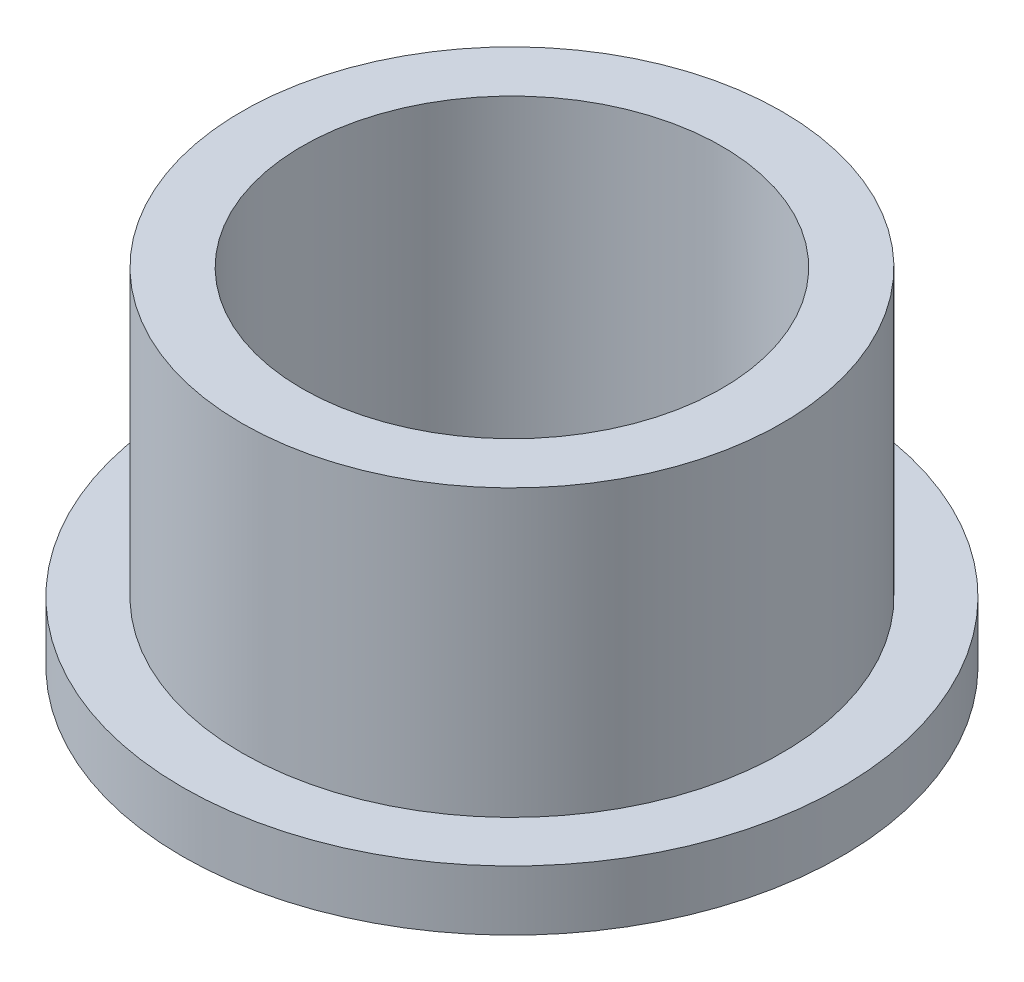
SolidWorks part; units mm, degrees
ref_plane "Front" through (0, 0, 0) normal (0, 0, 1) x (1, 0, 0)
ref_plane "Top" through (0, 0, 0) normal (0, 1, 0) x (1, 0, 0)
ref_plane "Right" through (0, 0, 0) normal (1, 0, 0) x (0, 0, -1)
sketch "Sketch1" plane through (0, 0, 0) normal (0, 1, 0) x (1, 0, 0)
  circle A0 centre (0, 0) radius 7.005
  circle A1 centre (0, 0) radius 9.015
  circle A2 centre (0, 0) radius 11
  dimension "ID" = 14.01
  dimension "OD" = 18.03
  dimension "FlangeOD" = 22
sketch "Sketch2" plane through (0, 0, 0) normal (0, 1, 0) x (1, 0, 0)
  circle A0 centre (0, 0) radius 7.005 construction
  circle A1 centre (0, 0) radius 9.015 construction
  circle A2 centre (0, 0) radius 7.005
  circle A3 centre (0, 0) radius 9.015
extrude "Boss-Extrude1" add sketch "Sketch2" along normal blind 14
sketch "Sketch3" plane through (0, 0, 0) normal (0, 1, 0) x (1, 0, 0)
  circle A0 centre (0, 0) radius 11 construction
  circle A1 centre (0, 0) radius 9.015 construction
  circle A2 centre (0, 0) radius 11
  circle A3 centre (0, 0) radius 9.015
extrude "Boss-Extrude2" add sketch "Sketch3" along normal blind 2
ref_axis "Center Axis 1" through (0, 14, 0) along (0, -1, 0)
sketch "Sketch4" plane through (0, 14, 0) normal (0, 1, 0) x (1, 0, 0)
  circle A0 centre (0, 0) radius 9.015
  circle A1 centre (0, 0) radius 9.015 construction
extrude "Cut-Extrude1" cut sketch "Sketch4" against normal blind 2.475
